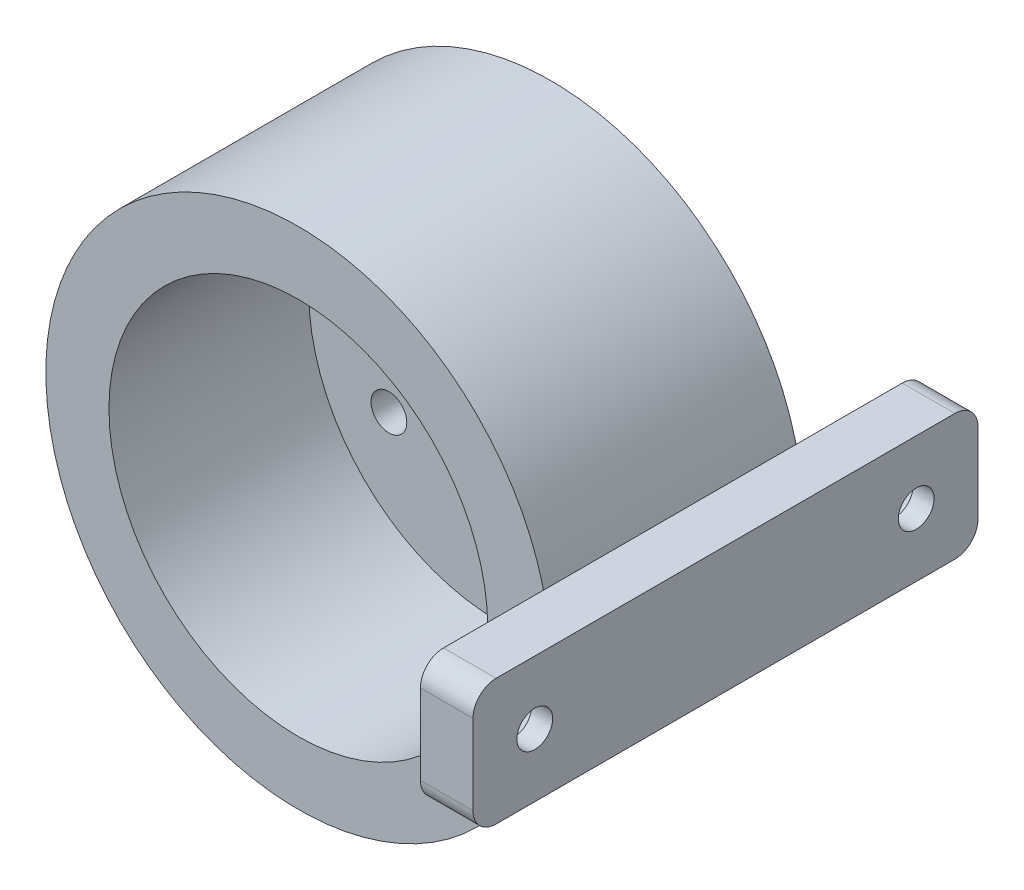
SolidWorks part; units mm, degrees
ref_plane "前视基准面" through (0, 0, 0) normal (0, 0, 1) x (1, 0, 0)
ref_plane "上视基准面" through (0, 0, 0) normal (0, 1, 0) x (1, 0, 0)
ref_plane "右视基准面" through (0, 0, 0) normal (1, 0, 0) x (0, 0, -1)
sketch "草图1" plane through (0, 0, 0) normal (0, 0, 1) x (1, 0, 0)
  circle A0 centre (0, 0) radius 9
  circle A1 centre (0, 0) radius 4
  circle A2 centre (0, 0) radius 2
  circle A4 centre (0, 6) radius 0.85
  circle A5 centre (-5.1962, -3) radius 0.85
  circle A6 centre (5.1962, -3) radius 0.85
  circle A7 centre (0, 0) radius 12
  circle A8 centre (0, 0) radius 4.3
  circle A9 centre (-5.1962, -3) radius 1.5
  circle A10 centre (5.1962, -3) radius 1.5
  circle A11 centre (0, 6) radius 1.5
extrude "凸台-拉伸1" add sketch "草图1" along normal blind 12 contours A7
extrude "切除-拉伸2" cut sketch "草图1<4>" along normal blind 2.5 contours A5 | A6 | A4
sketch "草图1<4>" plane through (0, 0, 0) normal (0, 0, 1) x (1, 0, 0) same geometry as "草图1"
extrude "凸台-拉伸2" add sketch "草图1<5>" against normal blind 4 contours A1
sketch "草图1<5>" plane through (0, 0, 0) normal (0, 0, 1) x (1, 0, 0) same geometry as "草图1"
extrude "凸台-拉伸3" add sketch "草图1<6>" against normal blind 0.5 contours A8
sketch "草图1<6>" plane through (0, 0, 0) normal (0, 0, 1) x (1, 0, 0) same geometry as "草图1"
extrude "切除-拉伸3" cut sketch "草图1<7>" against normal blind 4 contours A2
sketch "草图1<7>" plane through (0, 0, 0) normal (0, 0, 1) x (1, 0, 0) same geometry as "草图1"
extrude "切除-拉伸5" cut sketch "草图1<8>" along normal blind 1 contours A11 | A10 | A9
sketch "草图1<8>" plane through (0, 0, 0) normal (0, 0, 1) x (1, 0, 0) same geometry as "草图1"
extrude "切除-拉伸6" cut sketch "草图1<10>" against normal blind 9.5 from surface contours A0 starting at face at (12, 0, 12)
sketch "草图1<10>" plane through (0, 0, 0) normal (0, 0, 1) x (1, 0, 0) same geometry as "草图1"
ref_plane "基准面2" through (14, 0, 0) normal (1, 0, 0) x (0, 0, -1)
sketch "草图3" plane through (14, 0, 0) normal (1, 0, 0) x (0, 0, -1)
  line L0 (-12, 12) -> (0, -12)
  line L1 (0, 12) -> (-12, -12)
  line L2 (-13.1303, 0) -> (-14.0973, 1.675)
  line L7 (-14.0973, 1.675) -> (-16.0315, 1.675)
  line L8 (-16.0315, 1.675) -> (-16.9985, 0)
  line L13 (-16.9985, 0) -> (-16.0315, -1.675)
  line L14 (-16.0315, -1.675) -> (-14.0973, -1.675)
  line L15 (-12, 12) -> (-12, -12) construction
  line L18 (-14.0973, -1.675) -> (-13.1303, 0)
  line L19 (-6, 0) -> (-6, -2.5)
  line L20 (-12, -3) -> (-18, -3)
  line L21 (-18, -3) -> (-18, 3)
  line L23 (-18, 3) -> (-6, 3)
  line L24 (-6, 3) -> (-6, -3)
  line L25 (-6, -3) -> (-12, -3)
  line L27 (-6, -3) -> (0, -3)
  line L28 (-6, 3) -> (-6, -3)
  line L29 (6, 3) -> (-6, 3)
  line L30 (6, -3) -> (6, 3)
  line L31 (0, -3) -> (6, -3)
  line L32 (1.1303, 0) -> (2.0973, 1.675)
  line L33 (2.0973, 1.675) -> (4.0315, 1.675)
  line L34 (4.0315, 1.675) -> (4.9985, 0)
  line L35 (4.9985, 0) -> (4.0315, -1.675)
  line L36 (4.0315, -1.675) -> (2.0973, -1.675)
  line L37 (2.0973, -1.675) -> (1.1303, 0)
  circle A2 centre (-15.0644, 0) radius 1.675 construction
  circle A3 centre (3.0644, 0) radius 0.85
  circle A4 centre (3.0644, 0) radius 1.5
  circle A5 centre (3.0644, 0) radius 1.675 construction
  circle A6 centre (-15.0644, 0) radius 0.85
  circle A7 centre (-15.0644, 0) radius 1.5
  point P8 (-6, 0)
  point P13 (-6, 0)
  point P35 (-18, 0)
  point P36 (6, 0)
  point P37 (0, 0)
  point P48 (0, 0)
extrude "凸台-拉伸8" add sketch "草图3" against normal blind 2.2 and the other way blind 0.3 contours L23 L24 L25 L20 L21 | L29 L28 L27 L31 L30
extrude "切除-拉伸20" cut sketch "草图3<9>" along normal blind 1.5 from surface contours L2 L7 L8 L13 L14 L18 | L32 L33 L34 L35 L36 L37 starting at face at (11.8, 0, 6)
sketch "草图3<9>" plane through (14, 0, 0) normal (1, 0, 0) x (0, 0, -1) same geometry as "草图3"
extrude "切除-拉伸21" cut sketch "草图3<10>" against normal blind 2 and the other way blind 1 contours A6 | A3
sketch "草图3<10>" plane through (14, 0, 0) normal (1, 0, 0) x (0, 0, -1) same geometry as "草图3"
fillet "圆角3" radius 1.1 4 edges at (13.05, -3, -6) (13.05, 3, -6) (13.05, -3, 18) (13.05, 3, 18)
